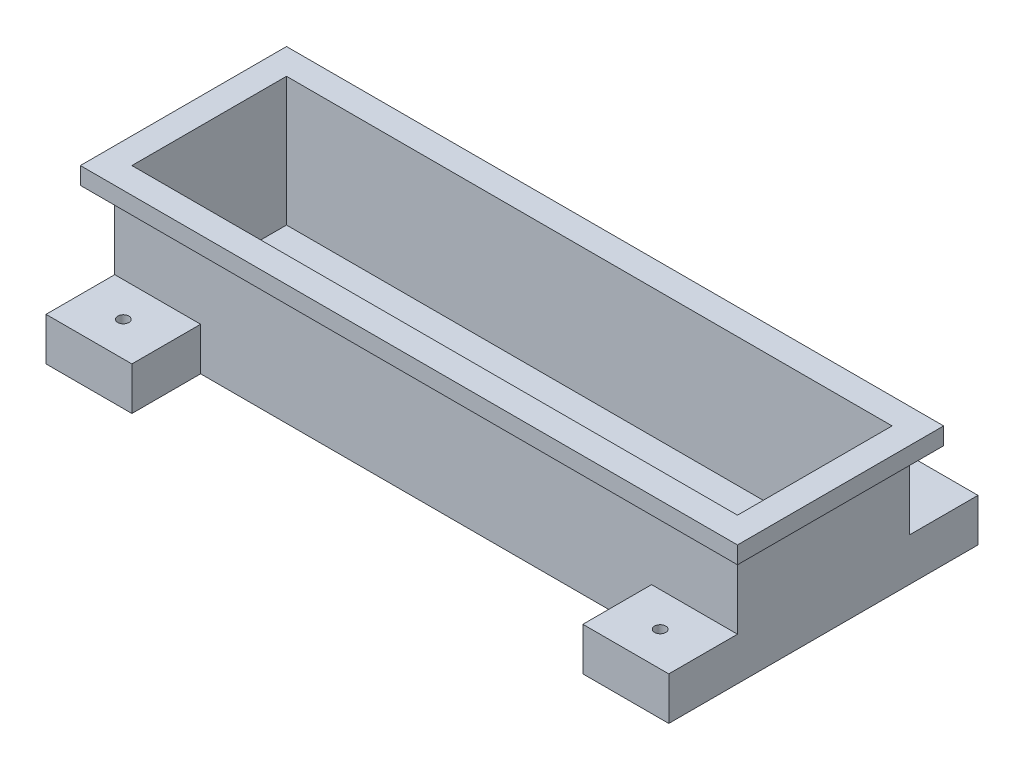
SolidWorks part; units mm, degrees
ref_plane "Front Plane" through (0, 0, 0) normal (0, 0, 1) x (1, 0, 0)
ref_plane "Top Plane" through (0, 0, 0) normal (0, 1, 0) x (1, 0, 0)
ref_plane "Right Plane" through (0, 0, 0) normal (1, 0, 0) x (0, 0, -1)
sketch "Sketch1" plane through (0, 0, 0) normal (0, 1, 0) x (1, 0, 0)
  line L0 (0, 0) -> (-72.5, 0) construction
  line L1 (-72.5, 20) -> (72.5, 20)
  line L2 (-72.5, 20) -> (-72.5, -20)
  line L3 (-72.5, -20) -> (72.5, -20)
  line L4 (72.5, 20) -> (72.5, -20)
  line L5 (0, 0) -> (0, 20) construction
  line L6 (-70.5, 18) -> (-70.5, -18)
  line L7 (-70.5, -18) -> (70.5, -18)
  line L8 (70.5, 18) -> (70.5, -18)
  line L9 (-70.5, 18) -> (70.5, 18)
  dimension "D1" = 145
  dimension "D2" = 40
  dimension "D3" = 2
extrude "Boss-Extrude1" add sketch "Sketch1" along normal blind 30
sketch "Sketch2" plane through (0, 0, 0) normal (0, -1, 0) x (1, 0, 0)
  line L4 (-72.5, 20) -> (-72.5, -20)
  line L5 (-72.5, -20) -> (72.5, -20)
  line L6 (72.5, -20) -> (72.5, 20)
  line L7 (72.5, 20) -> (-72.5, 20)
  line L8 (-72.5, 20) -> (-72.5, -20)
  line L9 (-72.5, -20) -> (72.5, -20)
  line L10 (72.5, -20) -> (72.5, 20)
  line L11 (72.5, 20) -> (-72.5, 20)
  dimension "D1" = 0
extrude "Boss-Extrude2" add sketch "Sketch2" along normal blind 2
sketch "Sketch3" plane through (0, 30, 0) normal (0, 1, 0) x (1, 0, 0)
  line L4 (72.5, -20) -> (72.5, 20) construction
  line L5 (-72.5, -20) -> (72.5, -20) construction
  line L6 (-72.5, 20) -> (-72.5, -20) construction
  line L7 (72.5, 20) -> (-72.5, 20) construction
  line L8 (-76.5, 24) -> (-76.5, -24)
  line L9 (-76.5, -24) -> (76.5, -24)
  line L10 (76.5, -24) -> (76.5, 24)
  line L11 (76.5, 24) -> (-76.5, 24)
  line L12 (-76.5, 24) -> (-76.5, -24)
  line L13 (-76.5, -24) -> (76.5, -24)
  line L14 (76.5, -24) -> (76.5, 24)
  line L15 (76.5, 24) -> (-76.5, 24)
  line L16 (72.5, -20) -> (72.5, 20)
  line L17 (-72.5, -20) -> (72.5, -20)
  line L18 (-72.5, 20) -> (-72.5, -20)
  line L19 (72.5, 20) -> (-72.5, 20)
  dimension "D1" = 4
extrude "Boss-Extrude3" add sketch "Sketch3" against normal blind 4
chamfer "Chamfer1" distance 4 angle 45 4 edges at (0, 26, -20) (72.5, 26, 0) (0, 26, 20) (-72.5, 26, 0)
sketch "Sketch4" plane through (0, -2, 0) normal (0, -1, 0) x (1, 0, 0)
  line L0 (72.5, 36) -> (52.5, 36)
  line L1 (-72.5, 20) -> (-52.5, 20)
  line L2 (-72.5, 20) -> (-72.5, 36)
  line L3 (-72.5, 36) -> (-52.5, 36)
  line L4 (-52.5, 20) -> (-52.5, 36)
  line L5 (0, 41.9362) -> (0, 0) construction
  line L6 (0, 0) -> (41.794, 0) construction
  line L7 (52.5, 20) -> (52.5, 36)
  line L8 (72.5, 20) -> (52.5, 20)
  line L9 (72.5, 20) -> (72.5, 36)
  line L10 (-72.5, -36) -> (-52.5, -36)
  line L11 (-52.5, -20) -> (-52.5, -36)
  line L12 (-72.5, -20) -> (-52.5, -20)
  line L13 (-72.5, -20) -> (-72.5, -36)
  line L14 (72.5, -20) -> (72.5, -36)
  line L15 (72.5, -20) -> (52.5, -20)
  line L16 (52.5, -20) -> (52.5, -36)
  line L17 (72.5, -36) -> (52.5, -36)
  line L18 (-62.5, 28) -> (-72.5, 28) construction
  line L19 (-62.5, 28) -> (-62.5, 36) construction
  circle A0 centre (-62.5, 28) radius 1.3
  circle A1 centre (-62.5, -28) radius 1.3
  circle A2 centre (62.5, 28) radius 1.3
  circle A3 centre (62.5, -28) radius 1.3
  point P27 (-58.8221, 28)
  dimension "D3" = 2.6
  dimension "D1" = 20
  dimension "D2" = 16
extrude "Boss-Extrude4" add sketch "Sketch4" against normal blind 10
